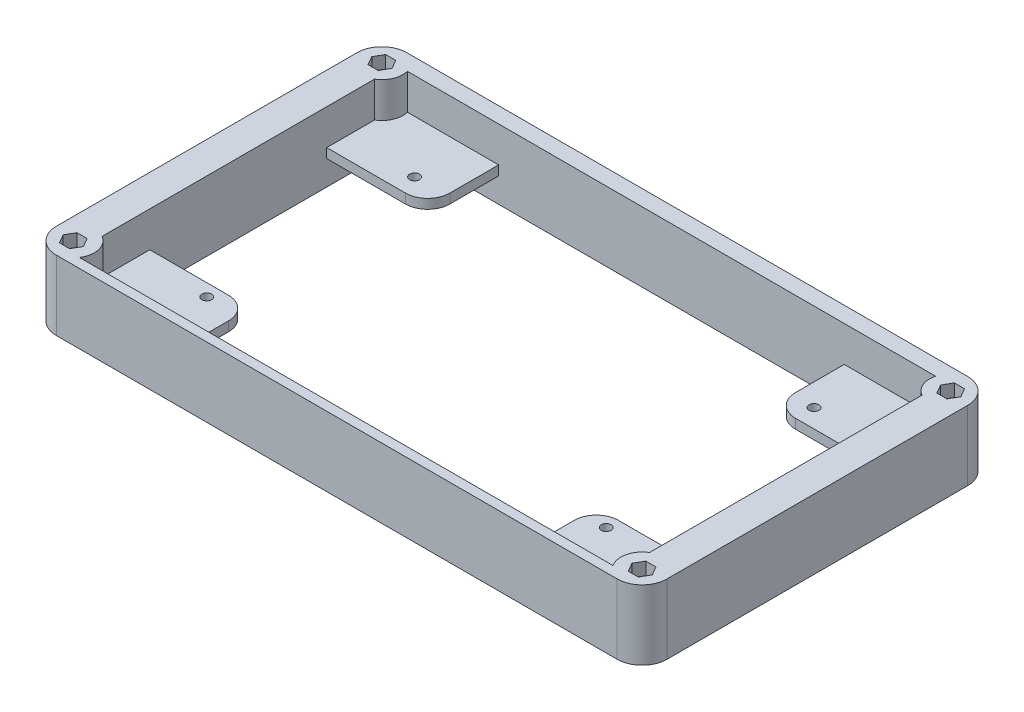
SolidWorks part; units mm, degrees
ref_plane "Alzado" through (0, 0, 0) normal (0, 0, 1) x (1, 0, 0)
ref_plane "Planta" through (0, 0, 0) normal (0, 1, 0) x (1, 0, 0)
ref_plane "Vista lateral" through (0, 0, 0) normal (1, 0, 0) x (0, 0, -1)
sketch "Croquis1" plane through (0, 0, 0) normal (0, 1, 0) x (1, 0, 0)
  line L1 (0, 0) -> (192.96, 0)
  line L2 (0, 0) -> (0, 110.76)
  line L3 (0, 110.76) -> (192.96, 110.76)
  line L4 (192.96, 0) -> (192.96, 110.76)
  line L5 (10, 105.76) -> (182.96, 105.76)
  line L6 (10, 105.76) -> (10, 3)
  line L7 (10, 3) -> (182.96, 3)
  line L8 (182.96, 105.76) -> (182.96, 3)
  dimension "D1" = 110.76
  dimension "D2" = 192.96
  dimension "D3" = 5
  dimension "D4" = 10
  dimension "D5" = 10
  dimension "D6" = 3
extrude "Saliente-Extruir2" add sketch "Croquis1" along normal blind 18
sketch "Croquis2" plane through (0, 0, -3) normal (0, 0, -1) x (-1, 0, 0)
  line L0 (-10, 18) -> (-10, 0) construction
  line L1 (-10, 7.8) -> (-41.89, 7.8)
  line L2 (-10, 7.8) -> (-10, 10.8)
  line L3 (-10, 10.8) -> (-41.89, 10.8)
  line L4 (-41.89, 7.8) -> (-41.89, 10.8)
  line L5 (-10, 0) -> (-182.96, 0) construction
  line L6 (0, 18) -> (0, 0) construction
  line L7 (-182.96, 18) -> (-182.96, 0) construction
  line L8 (-182.96, 7.8) -> (-151.07, 7.8)
  line L9 (-182.96, 7.8) -> (-182.96, 10.8)
  line L10 (-182.96, 10.8) -> (-151.07, 10.8)
  line L11 (-151.07, 7.8) -> (-151.07, 10.8)
  line L12 (-192.96, 18) -> (-192.96, 0) construction
  dimension "D1" = 3
  dimension "D2" = 7.8
  dimension "D3" = 41.89
  dimension "D4" = 41.89
extrude "Saliente-Extruir3" add sketch "Croquis2" along normal blind 24.43
sketch "Croquis3" plane through (0, 0, -105.76) normal (0, 0, 1) x (1, 0, 0)
  line L0 (182.96, 18) -> (182.96, 0) construction
  line L1 (182.96, 7.8) -> (151.07, 7.8)
  line L2 (182.96, 7.8) -> (182.96, 10.8)
  line L3 (182.96, 10.8) -> (151.07, 10.8)
  line L4 (151.07, 7.8) -> (151.07, 10.8)
  line L5 (151.07, 10.8) -> (182.96, 10.8) construction
  line L7 (151.07, 7.8) -> (151.07, 10.8) construction
  line L8 (10, 18) -> (10, 0) construction
  line L9 (10, 7.8) -> (41.89, 7.8)
  line L10 (10, 7.8) -> (10, 10.8)
  line L11 (10, 10.8) -> (41.89, 10.8)
  line L12 (41.89, 7.8) -> (41.89, 10.8)
  line L13 (41.89, 10.8) -> (41.89, 7.8) construction
  dimension "D1" = 3
  dimension "D2" = 0
  dimension "D3" = 0
  dimension "D4" = 0
extrude "Saliente-Extruir4" add sketch "Croquis3" along normal blind 22.43
sketch "Croquis5" plane through (0, 18, 0) normal (0, 1, 0) x (1, 0, 0)
extrude "Saliente-Extruir5" add sketch "Croquis1<2>" along normal blind 22
sketch "Croquis1<2>" plane through (0, 0, 0) normal (0, 1, 0) x (1, 0, 0) same geometry as "Croquis1"
sketch "Croquis6" plane through (0, 22, 0) normal (0, 1, 0) x (1, 0, 0)
  line L0 (0, 0) -> (192.96, 0) construction
  line L1 (0, 110.76) -> (0, 0) construction
  line L2 (192.96, 110.76) -> (0, 110.76) construction
  line L3 (192.96, 0) -> (192.96, 110.76) construction
  circle A0 centre (6.63, 6.63) radius 6.63
  circle A1 centre (6.63, 104.13) radius 6.63
  circle A2 centre (186.33, 104.13) radius 6.63
  circle A3 centre (186.33, 6.63) radius 6.63
  dimension "D1" = 6.63
  dimension "D2" = 6.63
  dimension "D3" = 6.63
  dimension "D4" = 6.63
extrude "Saliente-Extruir6" add sketch "Croquis6" against normal blind 22
sketch "Croquis7" plane through (0, 22, 0) normal (0, 1, 0) x (1, 0, 0)
  circle A0 centre (6.63, 104.13) radius 1.55
  circle A1 centre (186.33, 104.13) radius 1.55
  circle A2 centre (186.33, 6.63) radius 1.55
  circle A3 centre (6.63, 6.63) radius 1.55
extrude "Cortar-Extruir1" cut sketch "Croquis7" against normal blind 22
sketch "Croquis8" plane through (0, 22, 0) normal (0, 1, 0) x (1, 0, 0)
  line L1 (189.5343, 6.63) -> (187.9321, 9.405)
  line L2 (187.9321, 9.405) -> (184.7279, 9.405)
  line L3 (184.7279, 9.405) -> (183.1257, 6.63)
  line L4 (183.1257, 6.63) -> (184.7279, 3.855)
  line L5 (184.7279, 3.855) -> (187.9321, 3.855)
  line L6 (187.9321, 3.855) -> (189.5343, 6.63)
  line L7 (189.5343, 104.13) -> (187.9321, 106.905)
  line L8 (187.9321, 106.905) -> (184.7279, 106.905)
  line L9 (184.7279, 106.905) -> (183.1257, 104.13)
  line L10 (183.1257, 104.13) -> (184.7279, 101.355)
  line L11 (184.7279, 101.355) -> (187.9321, 101.355)
  line L12 (187.9321, 101.355) -> (189.5343, 104.13)
  line L13 (9.8343, 6.63) -> (8.2321, 9.405)
  line L14 (8.2321, 9.405) -> (5.0279, 9.405)
  line L15 (5.0279, 9.405) -> (3.4257, 6.63)
  line L16 (3.4257, 6.63) -> (5.0279, 3.855)
  line L17 (5.0279, 3.855) -> (8.2321, 3.855)
  line L18 (8.2321, 3.855) -> (9.8343, 6.63)
  line L19 (9.8343, 104.13) -> (8.2321, 106.905)
  line L20 (8.2321, 106.905) -> (5.0279, 106.905)
  line L21 (5.0279, 106.905) -> (3.4257, 104.13)
  line L22 (3.4257, 104.13) -> (5.0279, 101.355)
  line L23 (5.0279, 101.355) -> (8.2321, 101.355)
  line L24 (8.2321, 101.355) -> (9.8343, 104.13)
  circle A0 centre (186.33, 6.63) radius 2.775 construction
  circle A1 centre (186.33, 104.13) radius 2.775 construction
  circle A2 centre (6.63, 6.63) radius 2.775 construction
  circle A3 centre (6.63, 104.13) radius 2.775 construction
  dimension "D1" = 5.55
  dimension "D2" = 5.55
  dimension "D3" = 5.55
extrude "Cortar-Extruir2" cut sketch "Croquis8" against normal blind 4
fillet "Redondeo1" radius 7.88 1 edges at (0, 11, 0) type face fillet first side face at (0, 11, -55.38) second side face at (96.48, 11, 0)
fillet "Redondeo2" radius 7.88 1 edges at (0, 11, -110.76) type face fillet first side face at (0, 11, -59.32) second side face at (96.48, 11, -110.76)
fillet "Redondeo3" radius 7.88 1 edges at (192.96, 11, -110.76) type face fillet first side face at (100.42, 11, -110.76) second side face at (192.96, 11, -55.38)
fillet "Redondeo4" radius 7.88 1 edges at (192.96, 11, 0) type face fillet first side face at (192.96, 11, -51.44) second side face at (100.42, 11, 0)
sketch "Croquis9" plane through (0, 7.8, 0) normal (0, -1, 0) x (1, 0, 0)
  line L1 (185.08, -110.76) -> (7.88, -110.76) construction
  line L3 (0, -102.88) -> (0, -7.88) construction
  circle A0 centre (158.09, -89.18) radius 1.55
  circle A1 centre (158.09, -23.53) radius 1.55
  circle A2 centre (31.89, -89.18) radius 1.55
  circle A3 centre (31.89, -23.53) radius 1.55
  dimension "D1" = 126.2
  dimension "D3" = 65.65
  dimension "D4" = 31.89
  dimension "D5" = 126.2
  dimension "D2" = 21.58
  dimension "D6" = 31.89
  dimension "D7" = 65.65
extrude "Cortar-Extruir3" cut sketch "Croquis9" against normal blind 4
sketch "Croquis10" plane through (0, 0, 0) normal (0, -1, 0) x (1, 0, 0)
  line L0 (182.96, -12.3396) -> (182.96, -98.4204) construction
  line L1 (182.96, -105.76) -> (10, -105.76)
  line L2 (182.96, -105.76) -> (182.96, -3)
  line L3 (182.96, -3) -> (10, -3)
  line L4 (10, -105.76) -> (10, -3)
  line L5 (10, -98.4204) -> (10, -12.3396) construction
  line L6 (12.178, -3) -> (180.782, -3) construction
  line L7 (179.9035, -105.76) -> (13.0565, -105.76) construction
  dimension "D1" = 0
  dimension "D2" = 0
  dimension "D3" = 0
  dimension "D4" = 0
extrude "Cortar-Extruir5" cut sketch "Croquis10" against normal up to surface (7.8 mm away) up to face at (159.64, 7.8, -89.18)
fillet "Redondeo5" radius 7 1 edges at (151.07, 9.3, -27.43) type face fillet first side face at (151.07, 9.3, -15.215) second side face at (167.015, 9.3, -27.43)
fillet "Redondeo6" radius 7 1 edges at (151.07, 9.3, -83.33) type face fillet first side face at (167.015, 9.3, -83.33) second side face at (151.07, 9.3, -94.545)
fillet "Redondeo7" radius 7 1 edges at (41.89, 9.3, -83.33) type face fillet first side face at (25.945, 9.3, -83.33) second side face at (41.89, 9.3, -94.545)
fillet "Redondeo8" radius 7 1 edges at (41.89, 9.3, -27.43) type face fillet first side face at (25.945, 9.3, -27.43) second side face at (41.89, 9.3, -15.215)
sketch "Croquis11" plane through (0, 0, 0) normal (0, -1, 0) x (-1, 0, 0)
  line L0 (-10, 3) -> (-182.96, 3) construction
  line L1 (-136.48, 3) -> (-56.48, 3)
  line L2 (-136.48, 3) -> (-136.48, 1.5)
  line L3 (-136.48, 1.5) -> (-56.48, 1.5)
  line L4 (-56.48, 3) -> (-56.48, 1.5)
  line L5 (-192.96, 7.88) -> (-192.96, 102.88) construction
  dimension "D1" = 80
  dimension "D2" = 56.48
  dimension "D3" = 1.5
extrude "Cortar-Extruir6" cut sketch "Croquis11" against normal up to surface (7.8 mm away) up to face at (33.44, 7.8, -23.53)
fillet "Redondeo9" radius 1.5 1 edges at (96.48, 7.8, -1.5) type face fillet first side face at (96.48, 7.8, -2.25) second side face at (96.48, 3.9, -1.5)
